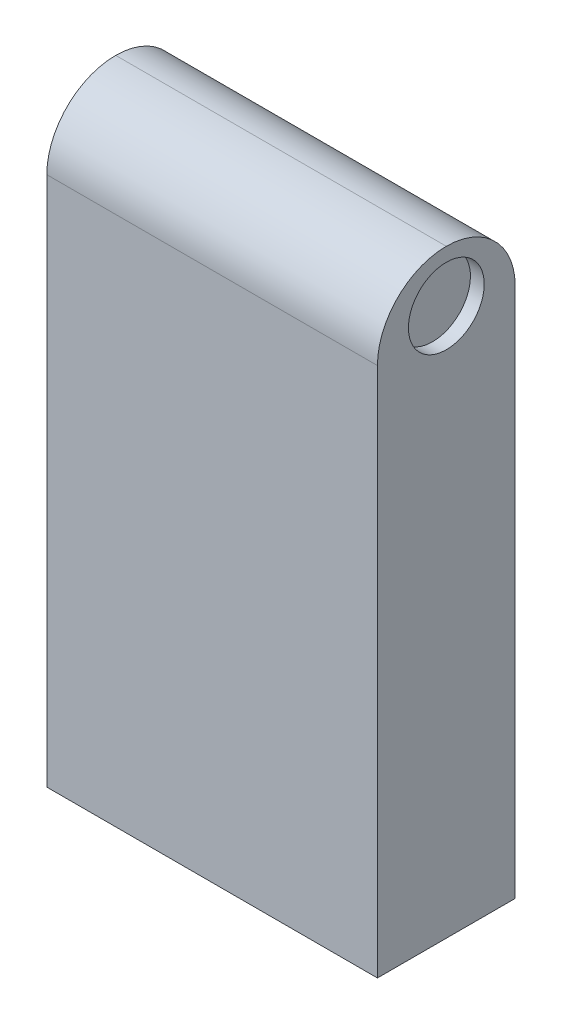
SolidWorks part; units mm, degrees
ref_plane "Front Plane" through (0, 0, 0) normal (0, 0, 1) x (1, 0, 0)
ref_plane "Top Plane" through (0, 0, 0) normal (0, 1, 0) x (1, 0, 0)
ref_plane "Right Plane" through (0, 0, 0) normal (1, 0, 0) x (0, 0, -1)
other "Center of Mass"
sketch "Sketch1" plane through (0, 0, 0) normal (0, 0, 1) x (1, 0, 0)
  line L1 (0, 0) -> (24, 0)
  line L2 (0, 0) -> (0, 43.5)
  line L3 (0, 43.5) -> (24, 43.5)
  line L4 (24, 0) -> (24, 43.5)
  dimension "D1" = 43.5
  dimension "D2" = 24
extrude "Boss-Extrude1" add sketch "Sketch1" along normal blind 10
fillet "Fillet1" radius 5 2 edges at (12, 43.5, 0) (12, 43.5, 10)
sketch "Sketch2" plane through (24, 0, 0) normal (1, 0, 0) x (0, 0, -1)
  line L0 (-5, 43.5) -> (-5, 12.9041) construction
  circle A0 centre (-5, 39.7454) radius 2.75
  dimension "D1" = 5.5
extrude "Cut-Extrude1" cut sketch "Sketch2" against normal blind 1
